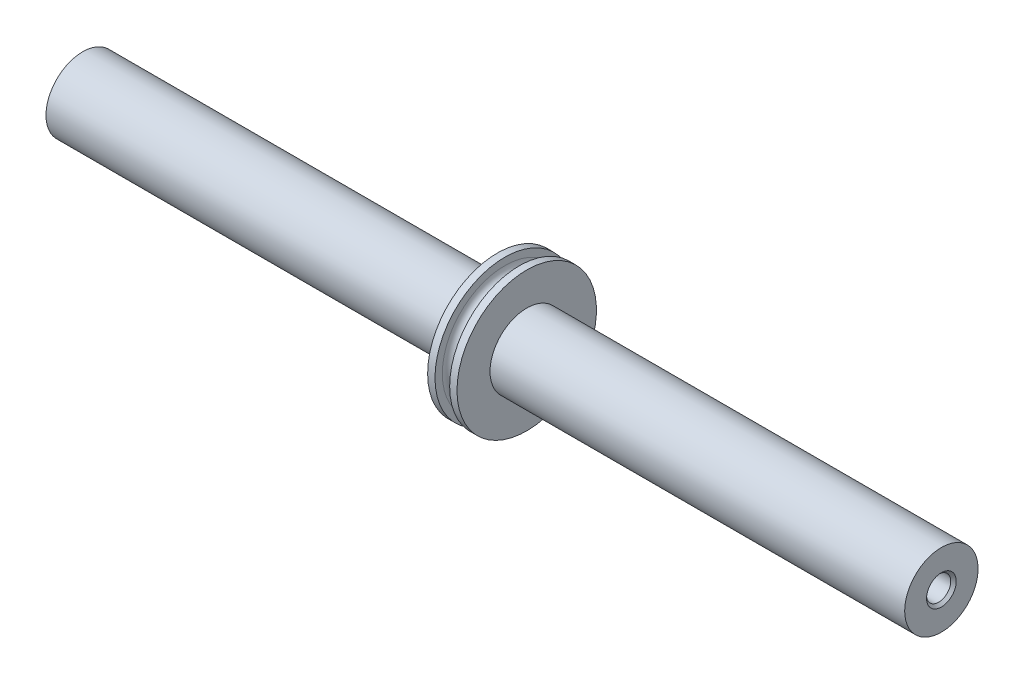
SolidWorks part; units mm, degrees
ref_plane "Front Plane" through (0, 0, 0) normal (0, 0, 1) x (1, 0, 0)
ref_plane "Top Plane" through (0, 0, 0) normal (0, 1, 0) x (1, 0, 0)
ref_plane "Right Plane" through (0, 0, 0) normal (1, 0, 0) x (0, 0, -1)
sketch "Sketch1" plane through (0, 0, 0) normal (0, 1, 0) x (1, 0, 0)
  line L0 (0, -55) -> (0, 55) construction
  line L1 (1, 0) -> (-1, 0)
  line L2 (0, 0) -> (0, 7.5)
  line L3 (1, 7.5) -> (-1, 7.5)
  line L4 (-1, 0) -> (-1, 7.5)
  line L5 (-1, 0) -> (-2, 0)
  line L6 (-1, 0) -> (-1, 9.5)
  line L7 (-1, 9.5) -> (-2, 9.5)
  line L8 (-2, 0) -> (-2, 9.5)
  line L9 (2, 0) -> (2, 9.5)
  line L10 (1, 9.5) -> (2, 9.5)
  line L11 (1, 0) -> (1, 9.5)
  line L12 (1, 0) -> (2, 0)
  line L13 (1, 0) -> (1, 7.5)
  line L14 (-2.6468, 0) -> (2.6468, 0) construction
  line L15 (2, 0) -> (58.5, 0)
  line L16 (-2, 0) -> (-58.5, 0)
  line L17 (-2, 0) -> (-2, 5)
  line L18 (-2, 5) -> (-58.5, 5)
  line L19 (-58.5, 0) -> (-58.5, 5)
  line L20 (58.5, 0) -> (58.5, 5)
  line L21 (2, 5) -> (58.5, 5)
  point P20 (0, 0)
  point P25 (0, 0)
  point P26 (0, 0)
  dimension "D1" = 7.5
  dimension "D2" = 1
  dimension "D3" = 1
  dimension "D4" = 2
  dimension "D6" = 117
  dimension "D7" = 10
revolve "Revolve1" add sketch "Sketch1" angle 360 about L14 region at (0.5, 0, -3.75) region at (1.5, 0, -4.75) region at (-0.5, 0, -3.75) region at (30.25, 0, -2.5) region at (-1.5, 0, -4.75) region at (-30.25, 0, -2.5)
fillet "Fillet1" radius 1 2 edges at (1, 0, 7.5) (-1, 0, 7.5)
hole_wizard "M4x0.7 Tapped Hole1" positions "3DSketch2" profile "Sketch3" tap size "M4x0.7" standard "ANSI Metric"
sketch3d "3DSketch2"
  circle A0 centre (-58.5, 0, 0) radius 5 construction
  point P0 (-58.5, 0, 0)
  point P3 (0, 0, 0)
  point P6 (-63.5, 0, 0)
sketch "Sketch3" plane through (-58.5, 0, 0) normal (0, 1, 0) x (0, 0, 1)
  line L0 (0, 0) -> (0, 15.9914)
  line L1 (0, 15.9914) -> (1.65, 15)
  line L2 (1.65, 15) -> (1.65, 0.375)
  line L3 (1.65, 0.375) -> (2.025, 0)
  line L5 (2.025, 0) -> (0, 0)
  line L6 (-1.65, 0.375) -> (-2.025, 0) construction
  line L10 (0, 15.9914) -> (-1.65, 15) construction
  line L11 (0, -6.35) -> (0, 107.95) construction
  dimension "Tap Drill Dia." = 3.3
  dimension "Tap Drill Depth" = 15
  dimension "Near C'Sink Dia." = 4.05
  dimension "Near C'Sink Angle" = 90
  dimension "Drill Angle" = 118
cosmetic thread "Hole Thread1" parameters "D1"=8, "D2"=4
mirror "Mirror1" about plane through (0, 0, 0) normal (1, 0, 0) of "M4x0.7 Tapped Hole1"
cosmetic thread "Hole Thread2" parameters "D1"=8, "D2"=4
